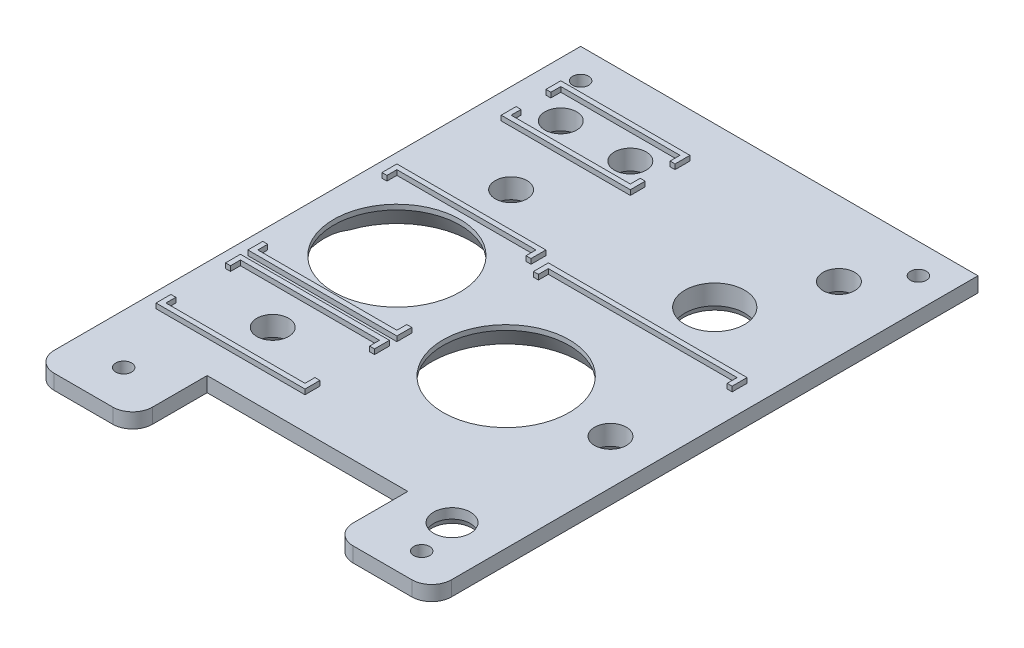
SolidWorks part; units mm, degrees
ref_plane "Спереди" through (0, 0, 0) normal (0, 0, 1) x (1, 0, 0)
ref_plane "Сверху" through (0, 0, 0) normal (0, 1, 0) x (1, 0, 0)
ref_plane "Справа" through (0, 0, 0) normal (1, 0, 0) x (0, 0, -1)
sketch "Sketch1" plane through (0, 0, 0) normal (0, 1, 0) x (1, 0, 0)
  line L1 (40, -55) -> (-40, -55)
  line L2 (40, -55) -> (40, 55)
  line L3 (40, 55) -> (-40, 55)
  line L4 (-40, -55) -> (-40, 55)
  line L5 (40, -55) -> (-40, 55) construction
  line L6 (40, 55) -> (-40, -55) construction
  point P0 (0, 0)
  dimension "D1" = 80
  dimension "D2" = 110
extrude "Boss-Extrude1" add sketch "Sketch1" along normal blind 3
sketch "Sketch2" plane through (0, 0, 55) normal (0, 0, 1) x (1, 0, 0)
  line L0 (0, 3) -> (0, 0) construction
  line L1 (-40, 3) -> (40, 3) construction
  line L2 (-40, 0) -> (40, 0) construction
  line L4 (20.2, 0) -> (-20.2, 0)
  line L5 (20.2, 0) -> (20.2, 3)
  line L6 (20.2, 3) -> (-20.2, 3)
  line L7 (-20.2, 0) -> (-20.2, 3)
  line L8 (20.2, 0) -> (-20.2, 3) construction
  line L9 (20.2, 3) -> (-20.2, 0) construction
  point P6 (0, 1.5)
  dimension "D1" = 40.4
extrude "Cut-Extrude1" cut sketch "Sketch2" against normal blind 15
fillet "Fillet1" radius 4 4 edges at (20.2, 1.5, 55) (40, 1.5, 55) (-20.2, 1.5, 55) (-40, 1.5, 55)
sketch "Sketch7" plane through (0, 0, 0) normal (0, -1, 0) x (1, 0, 0)
  line L0 (-40, -55) -> (-40, 51) construction
  line L1 (40, -55) -> (-40, -55) construction
  line L2 (36.8, 34.8) -> (-36.8, 34.8)
  line L3 (36.8, 34.8) -> (36.8, -51.8)
  line L4 (36.8, -51.8) -> (-36.8, -51.8)
  line L5 (-36.8, 34.8) -> (-36.8, -51.8)
  line L6 (36.8, 34.8) -> (-36.8, -51.8) construction
  line L7 (40, 51) -> (40, -55) construction
  line L8 (36.8, -51.8) -> (-36.8, 34.8) construction
  point P0 (0, -8.5)
  point P11 (0, 34.8)
  point P12 (0, -55)
  dimension "D1" = 3.2
  dimension "D2" = 3.2
  dimension "D3" = 3.2
  dimension "D4" = 89.8
extrude "Boss-Extrude2" add sketch "Sketch7" along normal blind 2
sketch "Sketch3" plane through (0, 3, 0) normal (0, 1, 0) x (1, 0, 0)
  line L0 (-40, 0) -> (40, 0) construction
  line L1 (-40, 55) -> (-40, -51) construction
  line L2 (40, -51) -> (40, 55) construction
  line L3 (-40, -10) -> (40, -10) construction
  line L4 (20.2, -40) -> (-20.2, -40) construction
  circle A0 centre (-22, 0) radius 12.7
  circle A1 centre (10, -10) radius 12.7
  point P10 (0, -10)
  point P13 (0, -40)
  point P16 (0, 0)
  dimension "D1" = 25.4
  dimension "D2" = 30
  dimension "D3" = 40
  dimension "D4" = 18
  dimension "D5" = 30
extrude "Cut-Extrude2" cut sketch "Sketch3" against normal through all
sketch "Sketch4" plane through (0, 3, 0) normal (0, 1, 0) x (1, 0, 0)
  line L0 (40, -51) -> (40, 55) construction
  line L1 (40, 55) -> (-40, 55) construction
  line L2 (19, 55) -> (19, -40) construction
  line L3 (40, -40) -> (-40, -40) construction
  line L4 (-40, 55) -> (-40, -51) construction
  line L5 (20.2, -40) -> (-20.2, -40) construction
  line L6 (40, 23) -> (-40, 23) construction
  line L7 (-22, 0) -> (-22, 55) construction
  line L8 (10, -10) -> (40, -10) construction
  line L9 (20.2, -41) -> (40, -41) construction
  line L10 (20.2, -40) -> (20.2, -51) construction
  line L11 (24.2, -55) -> (36, -55) construction
  line L12 (40, 40) -> (-40, 40) construction
  line L13 (-40, -25) -> (40, -25) construction
  line L15 (-22, 0) -> (-22, -54.3407) construction
  line L16 (-36, -55) -> (-24.2, -55) construction
  line L17 (-40, 49) -> (40, 49) construction
  line L18 (32, -41) -> (32, -55) construction
  line L19 (24.2, -55) -> (36, -55) construction
  circle A0 centre (19, 23) radius 6
  circle A1 centre (-22, 23) radius 3.2
  circle A2 centre (31, -10) radius 3.2
  circle A3 centre (30.1, -41) radius 3.7
  circle A4 centre (-29, 40) radius 3.2
  circle A5 centre (-15, 40) radius 3.2
  circle A6 centre (27, 40) radius 3.2
  circle A7 centre (-22, -25) radius 3.2
  arc A8 (-24.2, -55) -> (-20.2, -51) centre (-24.2, -51) ccw construction
  circle A9 centre (-30, -47) radius 1.6
  circle A10 centre (-34, 49) radius 1.6
  circle A11 centre (34, 49) radius 1.6
  circle A12 centre (32, -49) radius 1.6
  point P12 (0, -40)
  point P61 (0, 49)
  dimension "D1" = 12
  dimension "D7" = 7.4
  dimension "D8" = 14
  dimension "D14" = 6.4
  dimension "D17" = 3.2
  dimension "D20" = 3.2
  dimension "D25" = 3.2
  dimension "D27" = 13
  dimension "D2" = 21
  dimension "D3" = 32
  dimension "D6" = 9
  dimension "D12" = 14
  dimension "D13" = 7
  dimension "D15" = 30
  dimension "D16" = 15
  dimension "D18" = 10
  dimension "D19" = 8
  dimension "D21" = 68
  dimension "D22" = 34
  dimension "D23" = 6
  dimension "D24" = 8
  dimension "D26" = 6
extrude "Cut-Extrude3" cut sketch "Sketch4" against normal through all
chamfer "Chamfer2" distance 1.5 angle 20 4 edges at (36.8, -2, -8.5) (0, -2, -51.8) (-36.8, -2, -8.5) (0, -2, 34.8) first distance on face at (36.8, -1, -8.5) first distance on face at (0, -1, -51.8) first distance on face at (-36.8, -1, -8.5) first distance on face at (0, -1, 34.8)
chamfer "Chamfer3" distance 4 angle 30 2 edges at (-22, -2, 12.7) (10, -2, 22.7) first distance on face at (-22, -2, 12.7) first distance on face at (10, -2, 22.7)
sketch "Sketch8" plane through (0, 3, 0) normal (0, 1, 0) x (1, 0, 0)
  line L0 (-35, 43) -> (-35, 46)
  line L1 (-35, 46) -> (-9, 46)
  line L2 (-9, 46) -> (-9, 43)
  line L3 (-9, 43) -> (-10, 43)
  line L4 (-10, 43) -> (-10, 45)
  line L5 (-10, 45) -> (-34, 45)
  line L6 (-34, 45) -> (-34, 43)
  line L7 (-34, 43) -> (-35, 43)
  line L8 (-29, 40) -> (-15, 40) construction
  line L9 (31, -10) -> (10, -10) construction
  line L10 (10, -22.7) -> (10, 2.7) construction
  line L11 (-22, 45) -> (-22, 35) construction
  line L12 (-9, 37) -> (-9, 34)
  line L13 (-9, 34) -> (-35, 34)
  line L14 (-35, 34) -> (-35, 37)
  line L15 (-35, 37) -> (-34, 37)
  line L16 (-34, 37) -> (-34, 35)
  line L17 (-34, 35) -> (-10, 35)
  line L18 (-10, 35) -> (-10, 37)
  line L19 (-10, 37) -> (-9, 37)
  line L20 (-37, 12) -> (-37, 15)
  line L21 (-37, 15) -> (-7, 15)
  line L22 (-7, 15) -> (-7, 12)
  line L23 (-7, 12) -> (-8, 12)
  line L24 (-8, 12) -> (-8, 14)
  line L25 (-8, 14) -> (-36, 14)
  line L26 (-36, 14) -> (-36, 12)
  line L27 (-36, 12) -> (-37, 12)
  line L28 (-4.5, 10) -> (-4.5, 13)
  line L29 (-22, 14) -> (-22, -14) construction
  line L30 (-7, -12) -> (-7, -15)
  line L31 (-7, -15) -> (-37, -15)
  line L32 (-37, -15) -> (-37, -12)
  line L33 (-37, -12) -> (-36, -12)
  line L34 (-36, -12) -> (-36, -14)
  line L35 (-36, -14) -> (-8, -14)
  line L36 (-8, -14) -> (-8, -12)
  line L37 (-8, -12) -> (-7, -12)
  line L38 (-22, 12.7) -> (-22, -12.7) construction
  line L39 (-4.5, 13) -> (35.5, 13)
  line L40 (35.5, 13) -> (35.5, 10)
  line L41 (35.5, 10) -> (34.5, 10)
  line L42 (34.5, 10) -> (34.5, 12)
  line L43 (34.5, 12) -> (-3.5, 12)
  line L44 (-3.5, 12) -> (-3.5, 10)
  line L45 (-3.5, 10) -> (-4.5, 10)
  line L46 (15.5, 12) -> (15.5, -10) construction
  line L47 (-37, -19.5) -> (-37, -16.5)
  line L48 (-37, -16.5) -> (-7, -16.5)
  line L49 (-7, -16.5) -> (-7, -19.5)
  line L50 (-7, -19.5) -> (-8, -19.5)
  line L51 (-8, -19.5) -> (-8, -17.5)
  line L52 (-8, -17.5) -> (-36, -17.5)
  line L53 (-36, -17.5) -> (-36, -19.5)
  line L54 (-36, -19.5) -> (-37, -19.5)
  line L55 (-22, -17.5) -> (-22, -32.5) construction
  line L56 (-7, -30.5) -> (-7, -33.5)
  line L57 (-7, -33.5) -> (-37, -33.5)
  line L58 (-37, -33.5) -> (-37, -30.5)
  line L59 (-37, -30.5) -> (-36, -30.5)
  line L60 (-36, -30.5) -> (-36, -32.5)
  line L61 (-36, -32.5) -> (-8, -32.5)
  line L62 (-8, -32.5) -> (-8, -30.5)
  line L63 (-8, -30.5) -> (-7, -30.5)
  line L64 (-78.7082, -66.728) -> (-78.7082, -92.128) construction
  line L65 (-18.8, -25) -> (-25.2, -25) construction
  circle A1 centre (-22, 0) radius 12.7 construction
  circle A2 centre (10, -10) radius 12.7 construction
  circle A3 centre (-22, -25) radius 3.2 construction
  point P12 (-22, 40)
  point P15 (-22, 35)
  point P39 (-22, -14)
  point P51 (-22, 0)
  point P64 (-22, 0)
  point P66 (20.5, -10)
  point P81 (-22, -32.5)
  point P95 (-22, -25)
  point P96 (-22, -25)
  dimension "D1" = 1
  dimension "D2" = 1
  dimension "D3" = 26
  dimension "D4" = 3
  dimension "D5" = 10
  dimension "D6" = 30
  dimension "D7" = 28
  dimension "D8" = 40
  dimension "D9" = 5
  dimension "D10" = 22
  dimension "D11" = 15
  dimension "D12" = 1
  dimension "D13" = 1
extrude "Boss-Extrude3" add sketch "Sketch8" along normal blind 1
chamfer "Chamfer4" distance 1 angle 20 8 edges at (30.1, 0, 44.7) (31, -2, 13.2) (-22, -2, 28.2) (-22, -2, -19.8) (-29, -2, -36.8) (-15, -2, -36.8) (19, -2, -17) (27, -2, -36.8) first distance on face at (30.1, 3, 44.7) first distance on face at (31, -2, 13.2) first distance on face at (-22, -2, 28.2) first distance on face at (-22, -2, -19.8) first distance on face at (-29, -2, -36.8) first distance on face at (-15, -2, -36.8) first distance on face at (19, -2, -17) first distance on face at (27, -2, -36.8)
sketch "Sketch9" plane through (36.8, 0, 0) normal (1, 0, 0) x (0, 0, -1)
  line L1 (51.8, -0.5) -> (51.8, -2) construction
  line L2 (51.8, -2) -> (37.8915, -2) construction
  line L3 (51.254, -2) -> (-34.254, -2) construction
  line L5 (40.46, -2) -> (32.46, -2)
  line L6 (-34.8, -0.5) -> (51.8, -0.5) construction
  arc A0 (32.46, -2) -> (40.46, -2) centre (36.46, -6.5833) cw
  point P9 (36.46, -0.5)
  dimension "D1" = 8
  dimension "D2" = 15.34
extrude "Cut-Extrude4" cut sketch "Sketch9" against normal blind 4
sketch "Sketch10" plane through (-36.8, 0, 0) normal (-1, 0, 0) x (0, 0, 1)
  line L0 (-51.8, 0) -> (-51.8, -2) construction
  line L1 (-51.8, -2) -> (-35.7534, -2) construction
  line L2 (-4.7015, -2) -> (-51.254, -2) construction
  line L3 (-51.8, -0.5) -> (34.8, -0.5) construction
  line L5 (-40.46, -2) -> (-32.46, -2)
  arc A0 (-40.46, -2) -> (-32.46, -2) centre (-36.46, -6.5833) cw
  point P9 (-36.46, -0.5)
  dimension "D1" = 8
extrude "Cut-Extrude5" cut sketch "Sketch10" against normal blind 4
